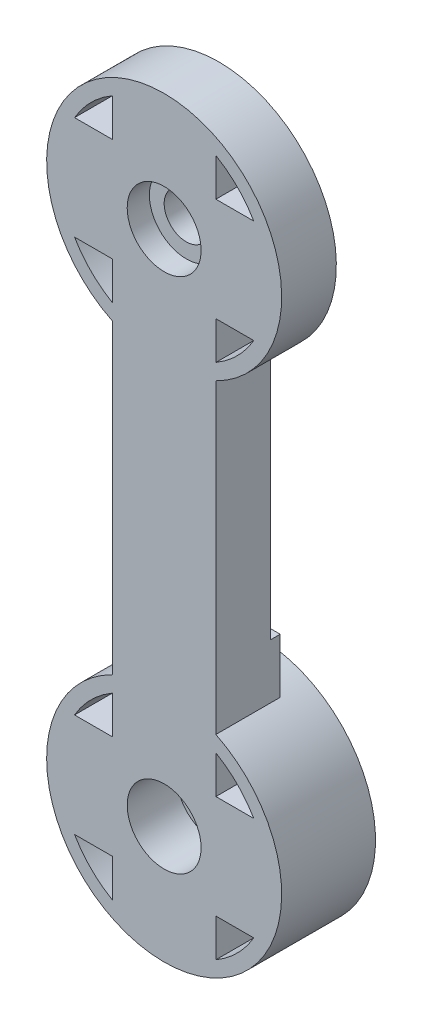
SolidWorks part; units mm, degrees
ref_plane "Front Plane" through (0, 0, 0) normal (0, 0, 1) x (1, 0, 0)
ref_plane "Top Plane" through (0, 0, 0) normal (0, 1, 0) x (1, 0, 0)
ref_plane "Right Plane" through (0, 0, 0) normal (1, 0, 0) x (0, 0, -1)
sketch "Sketch1" plane through (0, 0, 0) normal (0, 0, 1) x (1, 0, 0)
  line L5 (0, -17.5) -> (12.7696, -17.5) construction
  line L26 (0, 0) -> (0, -35) construction
  line L32 (0, 3.5) -> (7.1381, 3.5)
  line L33 (7.1381, 3.5) -> (-7.1381, 3.5)
  line L34 (0, -3.5) -> (7.1381, -3.5)
  line L35 (7.1381, -3.5) -> (-7.1381, -3.5)
  line L36 (3.5, -35) -> (3.5, -41.0622)
  line L37 (-3.5, -35) -> (-3.5, -41.0622)
  line L38 (-3.5, 0) -> (-3.5, 6.0622)
  line L45 (-3.5, 0) -> (-3.5, -35)
  line L47 (3.5, 0) -> (3.5, -35)
  line L48 (3.5, 0) -> (3.5, 6.0622)
  line L49 (7.1381, -31.5) -> (-7.1381, -31.5)
  line L50 (0, -31.5) -> (7.1381, -31.5)
  line L51 (7.1381, -38.5) -> (-7.1381, -38.5)
  line L52 (0, -38.5) -> (7.1381, -38.5)
  circle A0 centre (0, 0) radius 7.95
  circle A1 centre (0, 0) radius 3.5
  circle A2 centre (0, 0) radius 7
  circle A6 centre (0, 0) radius 1.5
  circle A11 centre (0, -35) radius 1.5
  circle A12 centre (0, -35) radius 7
  circle A13 centre (0, -35) radius 3.5
  circle A14 centre (0, -35) radius 7.95
  point P20 (0, -35)
  point P34 (0, -35)
  point P42 (0, 0)
  dimension "D1" = 15.9
  dimension "D2" = 7
  dimension "D6" = 14
  dimension "D9" = 3
  dimension "D3" = 7
  dimension "D7" = 35
extrude "Boss-Extrude4" add sketch "Sketch1" along normal blind 3 contours L48 A2 L38 L33 L32 | A2 L32 A0 L33 | L45 A14 L47 A0 | A14 L51 A12 | A12 L36 L51 L37 | A14 L49 A12 L51 | L36 A13 L51 | L51 A13 L37 | A14 L51 A12 L49 | A13 A11 | L45 A13 L49 | L49 A13 L47 | A12 L45 L49 L47 | A14 L49 A12 L45 | A14 L47 A12 L49 | A14 L45 A12 L47 | A12 L51 L37 L45 L49 | A12 L50 L47 L36 L52 | L45 A2 L47 L34 L35 | A2 L45 A0 L47 | A2 L47 A0 L34 | A2 L34 A0 L32 | A2 L33 A0 L35 | A2 L35 A0 L45 | L33 A2 L35 L45 L38 | L35 A2 L33 L48 L47 | A1 L34 L47 | A1 A6 | A1 L45 L35 | A1 L33 L38 | A1 L48 L32 region at (0, 5.1101, 0) region at (-2.7182, 2.7182, 0) region at (2.7182, 2.7182, 0) region at (2.4049, 2.4049, 0) region at (5.1101, 0, 0) region at (-5.1101, 0, 0) region at (2.7182, -2.7182, 0) region at (-2.7182, -2.7182, 0) region at (5.0555, 5.0555, 0) region at (7.1812, 0, 0) region at (-7.1812, 0, 0) region at (0, -5.1101, 0) region at (-5.2259, -5.2259, 0) region at (5.2259, -5.2259, 0) region at (0, -7.1812, 0) region at (0, -17.5, 0) region at (5.2259, -29.7741, 0) region at (0, -27.8188, 0) region at (-5.2259, -29.7741, 0) region at (0, -29.8899, 0) region at (7.1812, -35, 0) region at (-7.1812, -35, 0) region at (5.1101, -35, 0) region at (2.7182, -32.2818, 0) region at (-2.7182, -32.2818, 0) region at (-5.1101, -35, 0) region at (-6.6001, -38.6495, 0) region at (2.4049, -37.4049, 0) region at (2.7182, -37.7182, 0) region at (-2.7182, -37.7182, 0) region at (0, -40.1101, 0)
sketch "Sketch3" plane through (0, 0, 0) normal (0, 0, -1) x (-1, 0, 0)
  line L0 (-3.5, 6.0622) -> (-3.5, 3.5)
  line L1 (-3.5, 3.5) -> (-6.0622, 3.5)
  line L2 (-3.5, -6.0622) -> (-3.5, -3.5)
  line L3 (-3.5, -3.5) -> (-6.0622, -3.5)
  line L4 (3.5, -6.0622) -> (3.5, -3.5)
  line L5 (3.5, -3.5) -> (6.0622, -3.5)
  line L6 (3.5, 6.0622) -> (3.5, 3.5)
  line L7 (3.5, 3.5) -> (6.0622, 3.5)
  line L8 (0, 0) -> (0, -35) construction
  line L9 (0, -35) -> (0, -17.5) construction
  line L10 (0, -17.5) -> (14.5774, -17.5) construction
  line L11 (-3.5, 3.5) -> (-6.0622, 3.5)
  line L12 (-3.5, 6.0622) -> (-3.5, 3.5)
  line L13 (-3.5, -3.5) -> (-6.0622, -3.5)
  line L14 (-3.5, -6.0622) -> (-3.5, -3.5)
  line L15 (3.5, -3.5) -> (6.0622, -3.5)
  line L16 (3.5, -6.0622) -> (3.5, -3.5)
  line L17 (3.5, 3.5) -> (6.0622, 3.5)
  line L18 (3.5, 6.0622) -> (3.5, 3.5)
  line L19 (3.5, -41.0622) -> (3.5, -38.5)
  line L20 (3.5, -38.5) -> (6.0622, -38.5)
  line L21 (3.5, -28.9378) -> (3.5, -31.5)
  line L22 (3.5, -31.5) -> (6.0622, -31.5)
  line L23 (-3.5, -28.9378) -> (-3.5, -31.5)
  line L24 (-3.5, -31.5) -> (-6.0622, -31.5)
  line L25 (-3.5, -41.0622) -> (-3.5, -38.5)
  line L26 (-3.5, -38.5) -> (-6.0622, -38.5)
  line L27 (3.5, -38.5) -> (6.0622, -38.5)
  line L28 (3.5, -41.0622) -> (3.5, -38.5)
  line L29 (3.5, -31.5) -> (6.0622, -31.5)
  line L30 (3.5, -28.9378) -> (3.5, -31.5)
  line L31 (-3.5, -31.5) -> (-6.0622, -31.5)
  line L32 (-3.5, -28.9378) -> (-3.5, -31.5)
  line L33 (-3.5, -38.5) -> (-6.0622, -38.5)
  line L34 (-3.5, -41.0622) -> (-3.5, -38.5)
  circle A0 centre (0, 0) radius 1.5
  circle A1 centre (0, 0) radius 7.95
  circle A2 centre (0, 0) radius 7
  circle A3 centre (0, -35) radius 7
  circle A4 centre (0, -35) radius 7.95
  circle A5 centre (0, -35) radius 1.5
  line M2 (3.5, -38.5) -> (6.0622, -38.5)
  arc M3 (6.0622, -38.5) -> (3.5, -41.0622) centre (0, -35) cw
  line M4 (3.5, -41.0622) -> (3.5, -38.5)
  line M5 (-3.5, -38.5) -> (-3.5, -41.0622)
  arc M6 (-3.5, -41.0622) -> (-6.0622, -38.5) centre (0, -35) cw
  line M7 (-6.0622, -38.5) -> (-3.5, -38.5)
  arc M9 (3.5, -7.1381) -> (-3.5, -7.1381) centre (0, 0) ccw
  arc M11 (-3.5, -27.8619) -> (3.5, -27.8619) centre (0, -35) ccw
  line M12 (6.0622, -31.5) -> (3.5, -31.5)
  line M13 (3.5, -31.5) -> (3.5, -28.9378)
  arc M14 (3.5, -28.9378) -> (6.0622, -31.5) centre (0, -35) cw
  arc M15 (-3.5, -6.0622) -> (-6.0622, -3.5) centre (0, 0) cw
  line M16 (-6.0622, -3.5) -> (-3.5, -3.5)
  line M17 (-3.5, -3.5) -> (-3.5, -6.0622)
  line M18 (-3.5, -31.5) -> (-6.0622, -31.5)
  arc M19 (-6.0622, -31.5) -> (-3.5, -28.9378) centre (0, -35) cw
  line M20 (-3.5, -28.9378) -> (-3.5, -31.5)
  line M21 (3.5, -3.5) -> (6.0622, -3.5)
  arc M22 (6.0622, -3.5) -> (3.5, -6.0622) centre (0, 0) cw
  line M23 (3.5, -6.0622) -> (3.5, -3.5)
  line M24 (6.0622, 3.5) -> (3.5, 3.5)
  line M25 (3.5, 3.5) -> (3.5, 6.0622)
  arc M26 (3.5, 6.0622) -> (6.0622, 3.5) centre (0, 0) cw
  arc M27 (-6.0622, 3.5) -> (-3.5, 6.0622) centre (0, 0) cw
  line M28 (-3.5, 6.0622) -> (-3.5, 3.5)
  line M29 (-3.5, 3.5) -> (-6.0622, 3.5)
  circle M30 centre (0, 0) radius 1.5
  circle M31 centre (0, -35) radius 1.5
  dimension "D1" = 15.9
extrude "Boss-Extrude5" add sketch "Sketch3" along normal blind 3 contours A1 A2 M9 M26 M22 M15 M27 | A2 M25 M28 M29 M16 M17 M23 M21 M24 M30 | A3 M4 M2 M12 M13 M20 M18 M7 M5 M31 | A4 A3 M11 M3 M6 M19 M14 region at (0, 6.802, 0) region at (0, -41.802, 0) region at (-6.5556, -4.0868, 0) region at (4.0868, -41.5556, 0)
sketch "Sketch4" plane through (0, 0, 3) normal (0, 0, 1) x (1, 0, 0)
  line L0 (0, 0) -> (0, -35) construction
  line L1 (0, -35) -> (0, 0) construction
  line L2 (0, -17.5) -> (19.6941, -17.5) construction
  circle A1 centre (0, -35) radius 2.5
  circle A2 centre (0, 0) radius 2.5
  dimension "D2" = 5
extrude "Cut-Extrude1" cut sketch "Sketch4" against normal blind 1.5
sketch "Sketch5" plane through (0, 0, -3) normal (0, 0, -1) x (-1, 0, 0)
  circle A0 centre (0, 0) radius 7
extrude "Cut-Extrude2" cut sketch "Sketch5" against normal blind 2
sketch "Sketch6" plane through (0, 0, -3) normal (0, 0, -1) x (-1, 0, 0)
  circle A0 centre (0, -35) radius 7.95
extrude "Cut-Extrude3" cut sketch "Sketch6" against normal blind 1
sketch "Sketch7" plane through (0, 0, 1.5) normal (0, 0, 1) x (1, 0, 0)
  circle A0 centre (0, -35) radius 2.5
extrude "Cut-Extrude4" cut sketch "Sketch7" against normal blind 1.85
sketch "Sketch8" plane through (0, 0, -3) normal (0, 0, -1) x (-1, 0, 0)
  circle A0 centre (0, 0) radius 7.95
  circle A1 centre (0, 0) radius 7
extrude "Boss-Extrude6" add sketch "Sketch8" along normal blind 0.7
sketch "Sketch9" plane through (0, 0, -2) normal (0, 0, -1) x (-1, 0, 0)
  line L0 (-3.5, -28.9378) -> (-3.5, -31.5)
  line L1 (-3.5, -31.5) -> (-6.0622, -31.5)
  line L2 (-6.0622, -38.5) -> (-3.5, -38.5)
  line L3 (-3.5, -38.5) -> (-3.5, -41.0622)
  line L4 (6.0622, -38.5) -> (3.5, -38.5)
  line L5 (3.5, -38.5) -> (3.5, -41.0622)
  line L6 (3.5, -28.9378) -> (3.5, -31.5)
  line L7 (3.5, -31.5) -> (6.0622, -31.5)
  circle A0 centre (0, -35) radius 7.95
  circle A1 centre (0, -35) radius 7
  circle A2 centre (0, -35) radius 1.5
  line M1 (6.0622, -31.5) -> (3.5, -31.5)
  line M2 (3.5, -31.5) -> (3.5, -28.9378)
  arc M3 (3.5, -28.9378) -> (6.0622, -31.5) centre (0, -35) cw
  arc M4 (-3.5, -41.0622) -> (-6.0622, -38.5) centre (0, -35) cw
  line M5 (-6.0622, -38.5) -> (-3.5, -38.5)
  line M6 (-3.5, -38.5) -> (-3.5, -41.0622)
  arc M7 (6.0622, -38.5) -> (3.5, -41.0622) centre (0, -35) cw
  line M8 (3.5, -41.0622) -> (3.5, -38.5)
  line M9 (3.5, -38.5) -> (6.0622, -38.5)
  circle M10 centre (0, -35) radius 7.95
  line M11 (-3.5, -31.5) -> (-6.0622, -31.5)
  arc M12 (-6.0622, -31.5) -> (-3.5, -28.9378) centre (0, -35) cw
  line M13 (-3.5, -28.9378) -> (-3.5, -31.5)
  circle M14 centre (0, -35) radius 1.5
extrude "Boss-Extrude8" add sketch "Sketch9" along normal blind 0.7 contours A1 M2 M13 M11 M5 M6 M8 M9 M1 M14 | A1 M10 M3 M7 M4 M12 region at (0, -28.198, -2) region at (7.7251, -35, -2)
sketch "Sketch10" plane through (0, 0, 0) normal (0, 0, -1) x (-1, 0, 0)
  line L2 (-3.5, -7.1381) -> (-3.5, -27.8619)
  line L4 (3.5, -7.1381) -> (3.5, -27.8619)
  circle A0 centre (0, 0) radius 7.95
  circle A1 centre (0, -35) radius 7.95
  line M1 (-3.5, -7.1381) -> (-3.5, -27.8619)
  arc M2 (-3.5, -27.8619) -> (3.5, -27.8619) centre (0, -35) cw
  line M3 (3.5, -27.8619) -> (3.5, -7.1381)
  arc M4 (3.5, -7.1381) -> (-3.5, -7.1381) centre (0, 0) cw
extrude "Boss-Extrude9" add sketch "Sketch10" along normal blind 0.7 contours M4 M1 M2 M3 region at (0, -17.5, 0)
sketch "Sketch11" plane through (3.5, 0, 0) normal (1, 0, 0) x (0, 0, -1)
  line L0 (-3, -42.95) -> (2.7, -42.95) construction
  line L1 (3.7, 7.95) -> (0.7, 7.95)
  line L2 (3.7, 7.95) -> (3.7, -7.95)
  line L3 (3.7, -7.95) -> (0.7, -7.95)
  line L4 (0.7, 7.95) -> (0.7, -7.95)
  line L5 (2.7, -27.05) -> (0.7, -27.05)
  line L6 (2.7, -27.05) -> (2.7, -42.95)
  line L7 (2.7, -42.95) -> (0.7, -42.95)
  line L8 (0.7, -27.05) -> (0.7, -42.95)
extrude "Cut-Extrude5" cut sketch "Sketch11" against normal through all both and the other way through all
sketch "Sketch12" plane through (0, 0, -0.7) normal (0, 0, -1) x (-1, 0, 0)
  line L0 (3.5, -27.8619) -> (3.5, -7.1381) construction
  line L1 (-3.5, -27.8619) -> (3.5, -27.8619)
  line L2 (-3.5, -27.8619) -> (-3.5, -24.1619)
  line L3 (-3.5, -24.1619) -> (3.5, -24.1619)
  line L4 (3.5, -27.8619) -> (3.5, -24.1619)
  circle A0 centre (0, -35) radius 7.95
  line M3 (3.5, -27.8619) -> (3.5, -7.1381)
  line M5 (-3.5, -7.1381) -> (-3.5, -27.8619)
  dimension "D1" = 3.7
extrude "Boss-Extrude10" add sketch "Sketch12" along normal blind 0.65 contours A0 L3 M3 M5 region at (0, -25.7475, -0.7)
sketch "Sketch13" plane through (0, 0, -0.7) normal (0, 0, -1) x (-1, 0, 0)
  line L0 (-6.0622, -31.5) -> (-3.5, -31.5)
  line L1 (-3.5, -31.5) -> (-3.5, -28.9378)
  line L2 (3.5, -28.9378) -> (3.5, -31.5)
  line L3 (3.5, -31.5) -> (6.0622, -31.5)
  line L4 (-6.0622, -38.5) -> (-3.5, -38.5)
  line L5 (-3.5, -38.5) -> (-3.5, -41.0622)
  line L6 (6.0622, -38.5) -> (3.5, -38.5)
  line L7 (3.5, -38.5) -> (3.5, -41.0622)
  circle A0 centre (0, -35) radius 1.5
  circle A1 centre (0, -35) radius 7.95
  circle A2 centre (0, -35) radius 7
  arc M1 (-6.0622, -31.5) -> (-3.5, -28.9378) centre (0, -35) cw
  line M2 (-3.5, -28.9378) -> (-3.5, -31.5)
  line M3 (-3.5, -31.5) -> (-6.0622, -31.5)
  line M4 (3.5, -31.5) -> (3.5, -28.9378)
  arc M5 (3.5, -28.9378) -> (6.0622, -31.5) centre (0, -35) cw
  line M6 (6.0622, -31.5) -> (3.5, -31.5)
  line M7 (3.5, -38.5) -> (6.0622, -38.5)
  arc M8 (6.0622, -38.5) -> (3.5, -41.0622) centre (0, -35) cw
  line M9 (3.5, -41.0622) -> (3.5, -38.5)
  line M10 (-3.5, -38.5) -> (-3.5, -41.0622)
  arc M11 (-3.5, -41.0622) -> (-6.0622, -38.5) centre (0, -35) cw
  line M12 (-6.0622, -38.5) -> (-3.5, -38.5)
  circle M13 centre (0, -35) radius 1.5
  arc M14 (-3.5, -27.8619) -> (3.5, -27.8619) centre (0, -35) ccw
  arc M15 (3.5, -27.8619) -> (-3.5, -27.8619) centre (0, -35) ccw
extrude "Boss-Extrude11" add sketch "Sketch13" along normal blind 2.65 contours A2 M15 M14 M5 M8 M11 M1 | A2 M4 M2 M3 M12 M10 M9 M7 M6 M13 region at (4.7811, -31.698, -0.7) region at (4.0868, -41.5556, -0.7)
